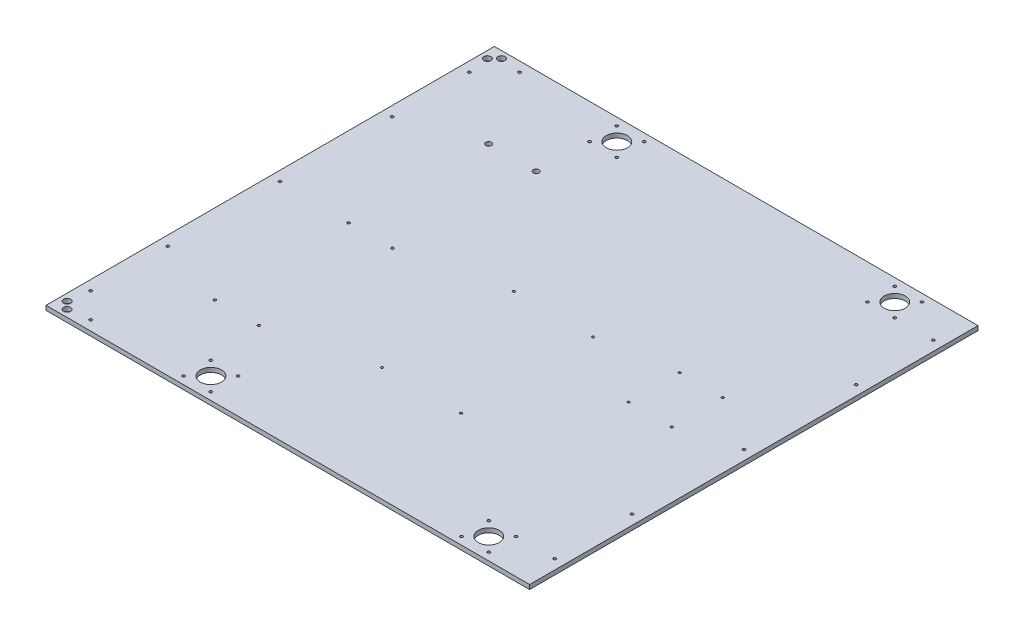
SolidWorks part; units mm, degrees
ref_plane "Front Plane" through (0, 0, 0) normal (0, 0, 1) x (1, 0, 0)
ref_plane "Top Plane" through (0, 0, 0) normal (0, 1, 0) x (1, 0, 0)
ref_plane "Right Plane" through (0, 0, 0) normal (1, 0, 0) x (0, 0, -1)
sketch "Sketch1" plane through (0, 0, 0) normal (1, 0, 0) x (0, 0, -1)
  line L0 (0, 0) -> (-510, 0)
  line L1 (-510, 0) -> (-510, 5)
  line L2 (-510, 5) -> (0, 5)
  line L6 (0, 5) -> (0, 0)
  dimension "D1" = 510
  dimension "D2" = 5
extrude "Boss-Extrude1" add sketch "Sketch1" along normal blind 550
sketch "BotthomHoles-Sketch2" plane through (0, 5, 0) normal (0, 1, 0) x (1, 0, 0)
  line L0 (550, -3.175) -> (0, -3.175) construction
  line L2 (550, 0) -> (550, -510) construction
  line L3 (550, 0) -> (0, 0) construction
  line L4 (550, -510) -> (0, -510) construction
  line L7 (0, 0) -> (0, -510) construction
  line L8 (550, 0) -> (550, -510) construction
  circle A0 centre (479.425, -24.175) radius 12
  circle A2 centre (463.925, -8.675) radius 1.5875
  circle A3 centre (494.925, -8.675) radius 1.5875
  circle A6 centre (463.925, -39.675) radius 1.5875
  circle A7 centre (494.925, -39.675) radius 1.5875
  circle A8 centre (39.6875, -11.1125) radius 1.5875
  circle A10 centre (178.925, -39.675) radius 1.5875
  circle A11 centre (147.925, -39.675) radius 1.5875
  circle A12 centre (178.925, -8.675) radius 1.5875
  circle A13 centre (147.925, -8.675) radius 1.5875
  circle A14 centre (163.425, -24.175) radius 12
  circle A15 centre (39.6875, -498.8875) radius 1.5875
  circle A16 centre (147.925, -501.325) radius 1.5875
  circle A17 centre (178.925, -501.325) radius 1.5875
  circle A18 centre (147.925, -470.325) radius 1.5875
  circle A19 centre (178.925, -470.325) radius 1.5875
  circle A20 centre (463.925, -470.325) radius 1.5875
  circle A21 centre (463.925, -501.325) radius 1.5875
  circle A22 centre (494.925, -470.325) radius 1.5875
  circle A23 centre (494.925, -501.325) radius 1.5875
  circle A25 centre (163.425, -485.825) radius 12
  circle A26 centre (479.425, -485.825) radius 12
  circle A27 centre (11.1125, -39.6875) radius 1.5875
  circle A28 centre (11.1125, -127.5) radius 1.5875
  circle A29 centre (11.1125, -255) radius 1.5875
  circle A30 centre (11.1125, -382.5) radius 1.5875
  circle A31 centre (11.1125, -470.3125) radius 1.5875
  circle A32 centre (538.8875, -470.3125) radius 1.5875
  circle A33 centre (538.8875, -382.5) radius 1.5875
  circle A34 centre (538.8875, -255) radius 1.5875
  circle A35 centre (538.8875, -127.5) radius 1.5875
  circle A36 centre (538.8875, -39.6875) radius 1.5875
  dimension "D9" = 3.175
  dimension "D10" = 24
  dimension "D13" = 3.175
  dimension "D29" = 3.175
  dimension "D2" = 8.675
  dimension "D5" = 15.5
  dimension "D6" = 31
  dimension "D7" = 15.5
  dimension "D8" = 31
  dimension "D11" = 21
  dimension "D12" = 39.6875
  dimension "D15" = 31
  dimension "D16" = 15.5
  dimension "D17" = 316
  dimension "D3" = 70.575
  dimension "D4" = 11.1125
  dimension "D18" = 8.675
  dimension "D19" = 15.5
  dimension "D20" = 31
  dimension "D21" = 11.1125
  dimension "D22" = 39.6875
  dimension "D23" = 39.6875
  dimension "D24" = 127.5
  dimension "D25" = 127.5
  dimension "D26" = 127.5
  dimension "D27" = 11.1125
  dimension "D28" = 11.1125
  dimension "D14" = 163.425
extrude "BottomEnclosureHoles-Cut-Extrude1" cut sketch "BotthomHoles-Sketch2" against normal through all
sketch "BottomPSUHolesSketch2" plane through (0, 5, 0) normal (0, 1, 0) x (1, 0, 0)
  line L0 (0, 0) -> (0, -510) construction
  line L3 (550, 0) -> (0, 0) construction
  line L4 (550, -510) -> (0, -510) construction
  circle A0 centre (90.8, -256.7) radius 1.5
  circle A1 centre (140.8, -256.7) radius 1.5
  circle A2 centre (90.8, -408.7) radius 1.5
  circle A3 centre (140.8, -408.7) radius 1.5
  circle A6 centre (92.8, -99.3) radius 3.25
  circle A7 centre (146.8, -99.3) radius 3.25
  dimension "D6" = 3
  dimension "D4" = 6.5
  dimension "D1" = 152
  dimension "D2" = 50
  dimension "D3" = 90.8
  dimension "D7" = 54
  dimension "D8" = 2
  dimension "D9" = 99.3
  dimension "D5" = 101.3
extrude "BottomPSUHolesCut-Extrude1" cut sketch "BottomPSUHolesSketch2" against normal through all
sketch "RPIHolesSketch2" plane through (0, 5, 0) normal (0, 1, 0) x (1, 0, 0)
  line L0 (550, 0) -> (0, 0) construction
  line L1 (0, 0) -> (0, -510) construction
  line L2 (550, 0) -> (550, -510) construction
  line L3 (550, -510) -> (0, -510) construction
  circle A4 centre (426.7, -216) radius 1.35
  circle A5 centre (475.7, -216) radius 1.35
  circle A6 centre (426.7, -274) radius 1.35
  circle A7 centre (475.7, -274) radius 1.35
  dimension "D7" = 2.7
  dimension "D4" = 58
  dimension "D5" = 49
  dimension "D8" = 216
  dimension "D10" = 74.3
  dimension "D11" = 236
  dimension "D2" = 426.7
extrude "RPIHolesCut-Extrude1" cut sketch "RPIHolesSketch2" against normal through all
sketch "CableHolesSketch2" plane through (0, 5, 0) normal (0, 1, 0) x (1, 0, 0)
  line L0 (550, 0) -> (0, 0) construction
  line L1 (550, -510) -> (0, -510) construction
  line L2 (0, 0) -> (0, -510) construction
  circle A0 centre (8, -494) radius 4
  circle A1 centre (16, -502) radius 4
  circle A2 centre (8, -16) radius 4
  circle A3 centre (16, -8) radius 4
  dimension "D6" = 8
  dimension "D1" = 16
  dimension "D2" = 16
  dimension "D3" = 16
  dimension "D4" = 8
  dimension "D5" = 8
  dimension "D7" = 8
extrude "CableHolesCut-Extrude1" cut sketch "CableHolesSketch2" against normal through all
sketch "OctopusHolesSketch2" plane through (0, 5, 0) normal (0, 1, 0) x (1, 0, 0)
  line L0 (0, 0) -> (0, -510) construction
  circle A0 centre (252.3, -230.2) radius 1.35
  circle A1 centre (252.3, -380.2) radius 1.35
  circle A2 centre (342.3, -230.2) radius 1.35
  circle A3 centre (342.3, -380.2) radius 1.35
  dimension "D3" = 2.7
  dimension "D1" = 150
  dimension "D2" = 90
  dimension "D4" = 111.5
  dimension "D5" = 26.5
  dimension "D6" = 252.3
  dimension "D7" = 129.8
extrude "OctopusHolesCut-Extrude1" cut sketch "OctopusHolesSketch2" against normal through all
equation "\"LowerRailWidth\"= 2.00in"
equation "\"RailThickness\"= .125in'Spec"
equation "\"StepperHoleDiameter\"= 24mm"
equation "\"StepperMountingHoleDiameter\"= 3.175mm"
equation "\"SideRailLength\"= 550mm"
equation "\"StepperMountingHoleDistance\"= 31mm'Spec"
equation "\"StepperMountingHoleOffsetFromLeftOrRightSide\"= \"StepperMountingHoleOffsetFromItsSide\" + \"RailThickness\""
equation "\"HoleOffsetFromEdge\"= \"RailThickness\" * 2.5"
equation "\"HoleOffsetFromSide\"= \"RailThickness\" * 3.5"
equation "\"StepperMountingHoleOffsetFromItsSide\"= 5.5mm'Spec"
equation "\"FasteningHoleDiameter\"= .125in"
equation "\"D2@BotthomHoles-Sketch2\" = \"StepperMountingHoleOffsetFromLeftOrRightSide\""
equation "\"D5@BotthomHoles-Sketch2\" = \"StepperMountingHoleDistance\" / 2"
equation "\"D6@BotthomHoles-Sketch2\" = \"StepperMountingHoleDistance\""
equation "\"D7@BotthomHoles-Sketch2\" = \"StepperMountingHoleDistance\" / 2"
equation "\"D8@BotthomHoles-Sketch2\" = \"StepperMountingHoleDistance\""
equation "\"D9@BotthomHoles-Sketch2\" = \"StepperMountingHoleDiameter\""
equation "\"D10@BotthomHoles-Sketch2\" = \"StepperHoleDiameter\""
equation "\"D1@Boss-Extrude1\"=\"SideRailLength\""
equation "\"BedThirdSize\"= 70mm"
equation "\"BedInnerSquareWidth\"= \"BedThirdSize\" * 3'Equals 210"
equation "\"BedInnerSquareLength\"= \"BedInnerSquareWidth\""
equation "\"BedLWidth\"= \"BedThirdSize\"'Equals 70"
equation "\"BedLength\"= \"BedInnerSquareLength\" + \"BedLWidth\" * 2 + \"BedIncreasedByLength\"'Equals 350"
equation "\"DistanceBetweenFrontToBackStepperHoles\"= \"BedLength\" - \"DistanceFromBedFrontToFirstLeftStepperHole\"'Equals 316"
equation "\"DistanceFromBedFrontToFirstLeftStepperHole\"= \"LeadScrewNutPadSize\" + 10mm'Equals 34"
equation "\"DistanceFromFrontSideToBedFront\"= \"RailThickness\" + \"BeltTensionerDepth\" + 10mm'Equals 36.575"
equation "\"20TGT2PulleyDiameter\"= 17.9mm'Spec"
equation "\"BeltTensionerBackWallThickness\"= 4mm"
equation "\"BeltTensionerSpaceBetweenPulleyAndWall\"= 1.5mm"
equation "\"BeltTensionerInnerDepth\"= \"20TGT2PulleyDiameter\" + \"BeltTensionerSpaceBetweenPulleyAndWall\""
equation "\"BeltTensionerDepth\"= \"BeltTensionerBackWallThickness\" + \"BeltTensionerInnerDepth\"'Equals 23.4"
equation "\"BedIncreasedByLength\"= 0mm"
equation "\"LowerCornerBlockWidth\"= \"LowerRailWidth\" - \"RailThickness\" * 2'Room for left front stepper"
equation "\"D12@BotthomHoles-Sketch2\"=\"CornerEnclosureOffset\""
equation "\"D13@BotthomHoles-Sketch2\"=\"FasteningHoleDiameter\""
equation "\"CornerEnclosureOffset\"= \"LowerCornerBlockWidth\" - \"HoleOffsetFromEdge\" + \"RailThickness\""
equation "\"LowerCornerBlockY1FromSide\"= \"HoleOffsetFromSide\""
equation "\"D15@BotthomHoles-Sketch2\"=\"StepperMountingHoleDistance\""
equation "\"D16@BotthomHoles-Sketch2\"=\"StepperMountingHoleDistance\"/2"
equation "\"D17@BotthomHoles-Sketch2\"=\"DistanceBetweenFrontToBackStepperHoles\""
equation "\"DistanceFromFrontSideToFirstLeftStepperHole\"= \"DistanceFromFrontSideToBedFront\" + \"DistanceFromBedFrontToFirstLeftStepperHole\"'Equals 70.575"
equation "\"LeadScrewNutMountingHoleFlangeDiameter\"= 22mm'Spec"
equation "\"LeadScrewNutPadSize\"= \"LeadScrewNutMountingHoleFlangeDiameter\" + 2mm'Equals 24"
equation "\"D3@BotthomHoles-Sketch2\"=\"DistanceFromFrontSideToFirstLeftStepperHole\""
equation "\"LowerEnclosureThickness\"= 5mm"
equation "\"FrontBackRailLength\"= 510mm"
equation "\"D4@BotthomHoles-Sketch2\"=\"LowerCornerBlockY1FromSide\""
equation "\"D1@Sketch1\"=\"FrontBackRailLength\""
equation "\"D18@BotthomHoles-Sketch2\"=\"StepperMountingHoleOffsetFromLeftOrRightSide\""
equation "\"D19@BotthomHoles-Sketch2\"=\"StepperMountingHoleDistance\"/2"
equation "\"D20@BotthomHoles-Sketch2\"=\"StepperMountingHoleDistance\""
equation "\"D21@BotthomHoles-Sketch2\"=\"LowerCornerBlockY1FromSide\""
equation "\"D22@BotthomHoles-Sketch2\"=\"CornerEnclosureOffset\""
equation "\"D23@BotthomHoles-Sketch2\"=\"CornerEnclosureOffset\""
equation "\"FrontOrBackEnclosureOffsets\"= \"FrontBackRailLength\" / 4"
equation "\"D24@BotthomHoles-Sketch2\"=\"FrontOrBackEnclosureOffsets\""
equation "\"D25@BotthomHoles-Sketch2\"=\"FrontOrBackEnclosureOffsets\""
equation "\"D26@BotthomHoles-Sketch2\"=\"FrontOrBackEnclosureOffsets\""
equation "\"D27@BotthomHoles-Sketch2\"=\"LowerCornerBlockY1FromSide\""
equation "\"D28@BotthomHoles-Sketch2\"=\"LowerCornerBlockY1FromSide\""
equation "\"D29@BotthomHoles-Sketch2\"=\"FasteningHoleDiameter\""
equation "\"D2@Sketch1\"=\"LowerEnclosureThickness\""
equation "\"24VPSUMountingHolesShortDistanceBetween\"= 50mm'Yours may differ"
equation "\"24VPSUMountingHolesLongDistanceBetween\"= 152mm'Yours may differ"
equation "\"24VPSUMountingHoleOffsetFromEitherSide\"= 30mm'Yours may differ"
equation "\"24VPSUMountingHoleOffsetFromEdge\"= \"24VPSUMountingHoleOffsetFromEitherSide\" + \"LowerRailWidth\" + 10mm'Yours may differ"
equation "\"24VPSUMountingHoleDiameter\"= 3mm'Yours may differ"
equation "\"D2@BottomPSUHolesSketch2\" = \"24VPSUMountingHolesShortDistanceBetween\""
equation "\"D1@BottomPSUHolesSketch2\" = \"24VPSUMountingHolesLongDistanceBetween\""
equation "\"D3@BottomPSUHolesSketch2\" = \"24VPSUMountingHoleOffsetFromEdge\""
equation "\"D6@BottomPSUHolesSketch2\" = \"24VPSUMountingHoleDiameter\""
equation "\"RPi4BoardLength\"= 85mm'Spec"
equation "\"RPi4BoardWidth\"= 56mm'Spec"
equation "\"RPi4BoardMountingHoleOffsetFromEdge\"= 3.5mm'Spec"
equation "\"RPi4BoardMountingHoleDiameter\"= 2.7mm'Spec"
equation "\"OctopusV1.1BoardMountingHoleOffsetFromAllEdges\"= 3.5mm'Spec"
equation "\"OctopusV1.1BoardMountingHoleLengthDistanceBetween\"= 150mm'Spec"
equation "\"OctopusV1.1BoardMountingHoleWidthDistanceBetween\"= 90mm'Spec"
equation "\"D4@RPIHolesSketch2\" = \"RPi4BoardMountingHoleLengthDistanceBetween\""
equation "\"D5@RPIHolesSketch2\" = \"RPi4BoardWidth\" - \"RPi4BoardMountingHoleOffsetFromEdge\" * 2"
equation "\"D7@RPIHolesSketch2\" = \"RPi4BoardMountingHoleDiameter\""
equation "\"RPi4BoardMountingHoleLengthDistanceBetween\"= 58mm'Spec"
equation "\"OctopusV1.1BoardMountingHoleDiameter\"= 2.7mm'Spec"
equation "\"D8@RPIHolesSketch2\" =  ( \"FrontBackRailLength\" - \"RPi4BoardLength\" )  / 2 + \"RPi4BoardMountingHoleOffsetFromEdge\""
equation "\"D10@RPIHolesSketch2\" = \"LowerRailWidth\" + \"RPi4BoardMountingHoleOffsetFromEdge\" + \"EnclosurePartsOffsetFromFrameInnerEdge\""
equation "\"RCNUN5VHeight\"= 57mm'Spec"
equation "\"RCNUN5VMountingHoleWidthDistance\"= 54mm'Spec. STL Is incorrect?"
equation "\"D7@BottomPSUHolesSketch2\"=\"RCNUN5VMountingHoleWidthDistance\""
equation "\"D8@BottomPSUHolesSketch2\"=(\"RCNUN5VMountingHoleWidthDistance\" - \"24VPSUMountingHolesShortDistanceBetween\")/2"
equation "\"D9@BottomPSUHolesSketch2\"=\"LowerRailWidth\" + \"RCNUN5VHeight\"/2 + \"EnclosurePartsOffsetFromFrameInnerEdge\""
equation "\"EnclosurePartsOffsetFromFrameInnerEdge\"= 20mm"
equation "\"D5@BottomPSUHolesSketch2\"= \"LowerRailWidth\" + \"EnclosurePartsOffsetFromFrameInnerEdge\" + ( \"24VPSULength\" - \"24VPSUMountingHolesLongDistanceBetween\" ) / 2"
equation "\"24VPSULength\"= 213mm'Spec"
equation "\"LowerRailCableHoleDiameter\"= 8mm"
equation "\"LowerRailCableHoleOffsetFromSide\"= 8mm"
equation "\"LowerRailCableHoleOffsetFromEdge\"= 16mm"
equation "\"D1@CableHolesSketch2\"=\"LowerRailCableHoleOffsetFromEdge\""
equation "\"D2@CableHolesSketch2\"=\"LowerRailCableHoleOffsetFromEdge\""
equation "\"D3@CableHolesSketch2\"=\"LowerRailCableHoleOffsetFromEdge\""
equation "\"D4@CableHolesSketch2\"=\"LowerRailCableHoleOffsetFromSide\""
equation "\"D5@CableHolesSketch2\"=\"LowerRailCableHoleOffsetFromSide\""
equation "\"D6@CableHolesSketch2\"=\"LowerRailCableHoleDiameter\""
equation "\"D7@CableHolesSketch2\"=\"LowerRailCableHoleOffsetFromSide\""
equation "\"D1@OctopusHolesSketch2\"=\"OctopusV1.1BoardMountingHoleLengthDistanceBetween\""
equation "\"D2@OctopusHolesSketch2\"=\"OctopusV1.1BoardMountingHoleWidthDistanceBetween\""
equation "\"D3@OctopusHolesSketch2\"=\"OctopusV1.1BoardMountingHoleDiameter\""
equation "\"24VPSUMountingHoleOffsetFromFront\"= 30mm"
equation "\"D5@OctopusHolesSketch2\"=\"24VPSUMountingHoleOffsetFromFront\" - \"OctopusV1.1BoardMountingHoleOffsetFromAllEdges\""
equation "\"DistanceBetween24VPSUAndOctopus\"= \"24VPSUMountingHoleOffsetFromEitherSide\" + \"OctopusV1.1BoardMountingHoleOffsetFromAllEdges\" + 78'78mm gave me a nice distance to print a cable guide"
equation "\"D4@OctopusHolesSketch2\"=\"DistanceBetween24VPSUAndOctopus\""
